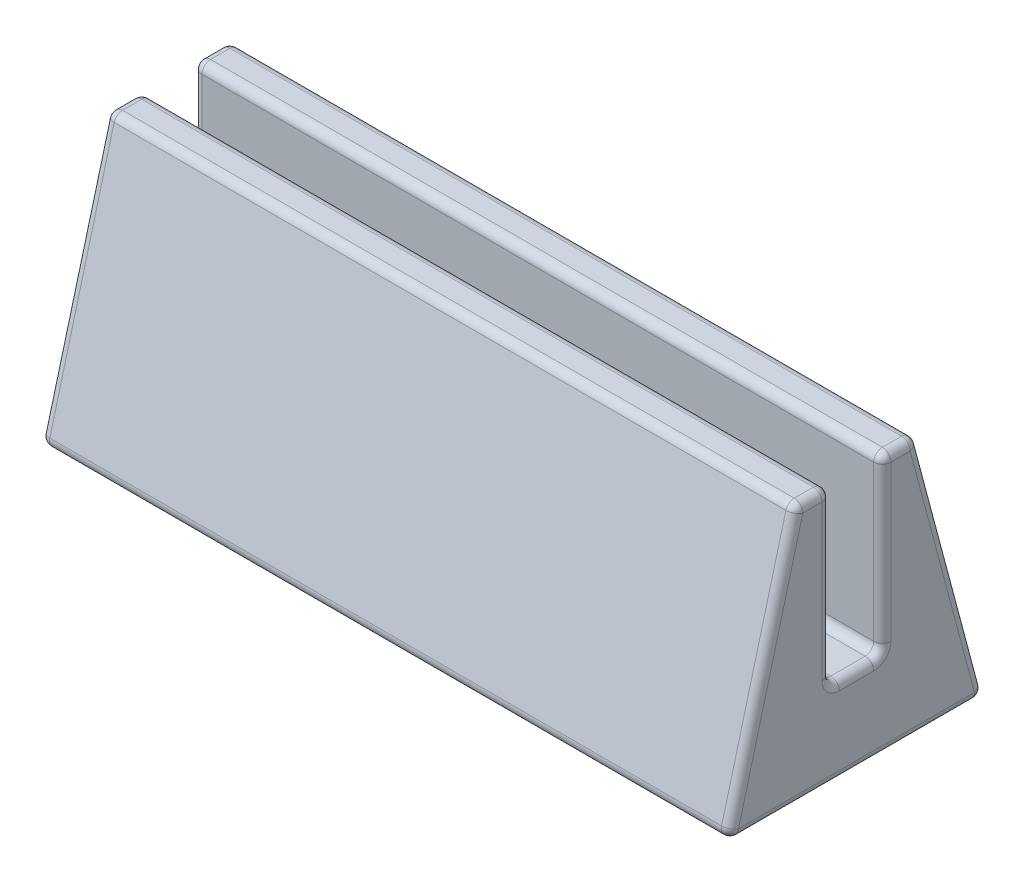
SolidWorks part; units mm, degrees
ref_plane "Front Plane" through (0, 0, 0) normal (0, 0, 1) x (1, 0, 0)
ref_plane "Top Plane" through (0, 0, 0) normal (0, 1, 0) x (1, 0, 0)
ref_plane "Right Plane" through (0, 0, 0) normal (1, 0, 0) x (0, 0, -1)
sketch "Sketch1" plane through (0, 0, 0) normal (1, 0, 0) x (0, 0, -1)
  line L0 (-15, 0) -> (15, 0)
  line L1 (-15, 0) -> (-7, 30)
  line L2 (-7, 30) -> (-3, 30)
  line L3 (-3, 30) -> (-3, 10)
  line L4 (-3, 10) -> (3, 10)
  line L5 (0, 10) -> (0, 19.2396) construction
  line L6 (15, 0) -> (7, 30)
  line L7 (7, 30) -> (3, 30)
  line L8 (3, 30) -> (3, 10)
  point P4 (0, 0)
  dimension "D1" = 30
  dimension "D2" = 30
  dimension "D3" = 7
  dimension "D4" = 4
  dimension "D5" = 20
extrude "Boss-Extrude1" add sketch "Sketch1" along normal mid plane 80
fillet "Fillet1" radius 1 24 edges at (0, 10, 3) (0, 30, 3) (0, 30, 7) (0, 0, 15) (0, 0, -15) (0, 30, -7) (0, 30, -3) (0, 10, -3) (40, 20, -3) (40, 30, -5) (40, 15, -11) (40, 0, 0) (40, 15, 11) (40, 30, 5) (40, 20, 3) (40, 10, 0) (-40, 20, -3) (-40, 30, -5) (-40, 15, -11) (-40, 0, 0) (-40, 15, 11) (-40, 30, 5) (-40, 20, 3) (-40, 10, 0)
